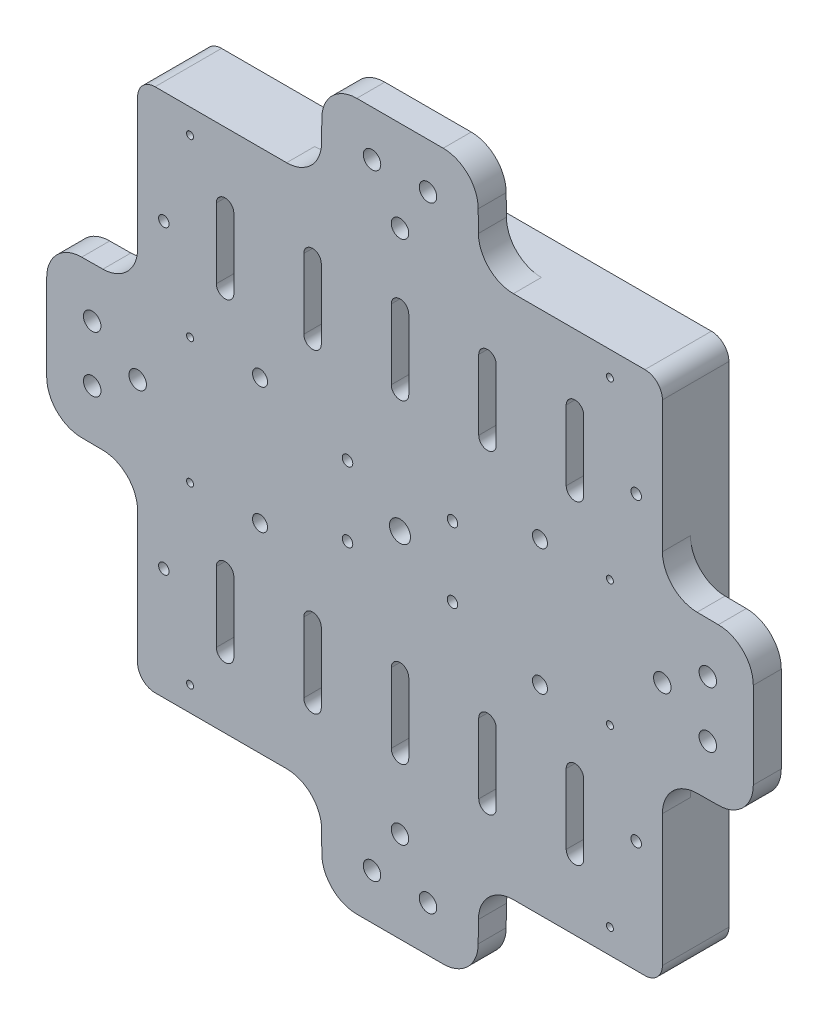
SolidWorks part; units mm, degrees
ref_plane "Front Plane" through (0, 0, 0) normal (0, 0, 1) x (1, 0, 0)
ref_plane "Top Plane" through (0, 0, 0) normal (0, 1, 0) x (1, 0, 0)
ref_plane "Right Plane" through (0, 0, 0) normal (1, 0, 0) x (0, 0, -1)
sketch "Sketch1" plane through (0, 0, 0) normal (0, 0, 1) x (1, 0, 0)
  line L13 (-90, -90) -> (90, -90)
  line L14 (-90, -90) -> (-90, 90)
  line L15 (-90, 90) -> (90, 90)
  line L16 (90, -90) -> (90, 90)
  line L17 (-90, -90) -> (90, 90) construction
  line L18 (-90, 90) -> (90, -90) construction
  line L19 (-75, -75) -> (75, -75)
  line L20 (-75, -75) -> (-75, 75)
  line L21 (-75, 75) -> (75, 75)
  line L22 (75, -75) -> (75, 75)
  line L23 (-75, -75) -> (75, 75) construction
  line L24 (-75, 75) -> (75, -75) construction
  line L39 (-75, -24.9122) -> (-75, 26.5574)
  line L40 (75, 22.5) -> (75, -22.5)
  line L41 (75, -22.5) -> (90.9698, -22.3479)
  line L42 (90.9698, -22.3479) -> (90.9698, 22.3479)
  line L43 (90.9698, 22.3479) -> (75, 22.5)
  line L44 (22.3479, -90.9698) -> (22.5, -75)
  line L45 (22.5, -75) -> (-22.5, -75)
  line L46 (-22.5, -75) -> (-22.3479, -90.9698)
  line L47 (-22.3479, -90.9698) -> (22.3479, -90.9698)
  line L48 (-90.9698, -22.3479) -> (-75, -22.5)
  line L49 (-75, -22.5) -> (-75, 22.5)
  line L50 (-75, 22.5) -> (-90.9698, 22.3479)
  line L51 (-90.9698, 22.3479) -> (-90.9698, -22.3479)
  line L52 (-22.3479, 90.9698) -> (-22.5, 75)
  line L53 (-22.5, 75) -> (22.5, 75)
  line L54 (22.5, 75) -> (22.3479, 90.9698)
  line L55 (22.3479, 90.9698) -> (-22.3479, 90.9698)
  line L64 (-72, -72) -> (-72, 72)
  line L65 (-72, 72) -> (72, 72)
  line L70 (72, -72) -> (72, 72)
  line L71 (-72, -72) -> (72, -72)
  line L72 (-10.5, -75) -> (10.5, -75)
  line L77 (75, -10.5) -> (64, -10.5)
  line L78 (75, -10.5) -> (75, 10.5)
  line L79 (75, 10.5) -> (64, 10.5)
  line L80 (64, -10.5) -> (64, 10.5)
  line L81 (-10.5, -75) -> (-10.5, -64)
  line L82 (-10.5, -64) -> (10.5, -64)
  line L83 (10.5, -75) -> (10.5, -64)
  line L84 (-75, 10.5) -> (-75, -10.5)
  line L85 (-75, 10.5) -> (-64, 10.5)
  line L86 (-64, 10.5) -> (-64, -10.5)
  line L87 (-75, -10.5) -> (-64, -10.5)
  line L88 (10.5, 75) -> (-10.5, 75)
  line L89 (10.5, 75) -> (10.5, 64)
  line L90 (10.5, 64) -> (-10.5, 64)
  line L91 (-10.5, 75) -> (-10.5, 64)
  line L92 (-75, 45) -> (-72, 45)
  line L93 (-45, 75) -> (-45, 72)
  circle A0 centre (87.9698, 8) radius 2.5
  circle A1 centre (74.9698, 0) radius 2.5
  circle A2 centre (87.9698, -8) radius 2.5
  circle A3 centre (8, -87.9698) radius 2.5
  circle A4 centre (0, -74.9698) radius 2.5
  circle A5 centre (-8, -87.9698) radius 2.5
  circle A6 centre (-87.9698, -8) radius 2.5
  circle A7 centre (-74.9698, 0) radius 2.5
  circle A8 centre (-87.9698, 8) radius 2.5
  circle A9 centre (-8, 87.9698) radius 2.5
  circle A10 centre (0, 74.9698) radius 2.5
  circle A11 centre (8, 87.9698) radius 2.5
  circle A12 centre (0, 0) radius 3
  point P0 (0, 0)
  point P11 (0, 0)
  point P74 (64, 0)
  point P85 (0, 0)
  dimension "D3" = 4
  dimension "D12" = 6
  dimension "D1" = 180
  dimension "D2" = 180
  dimension "D4" = 150
  dimension "D5" = 4
  dimension "D6" = 3
  dimension "D8" = 11
  dimension "D7" = 21
  dimension "D10" = 45
  dimension "D11" = 45
  dimension "D9" = 4
extrude "Boss-Extrude1" add sketch "Sketch1" along normal mid plane 8 contours L83 L19 L22 L77 L70 L71 | A2 L16 A0 L43 L22 L40 A1 L41 | L80 L77 L70 L79 | L91 L65 L64 L85 L86 L87 L71 L81 L82 L83 L70 L77 L80 L79 L89 L90 A12 | L21 L89 L65 L70 L79 L22 | L65 L91 L90 L89 | A10 L53 L91 L65 L89 | A11 L15 A9 L52 L21 L53 A10 L54 | A11 L15 L54 L55 L52 A9 | A8 L14 A6 L48 L39 L49 A7 L50 | L92 L20 L39 L85 L64 | L93 L21 L20 L92 L64 L65 | A5 L13 A3 L44 L19 L45 A4 L46 | A5 L13 L46 L47 L44 A3 | A4 L45 L83 L71 L81 | L71 L83 L82 L81 | A1 L40 L79 L70 L77 | A2 L16 L41 L42 L43 A0 | A8 L14 L50 L51 L48 A6 | L64 L87 L86 L85 | A7 L49 L87 L64 L85 | L87 L39 L20 L19 L81 L71 L64 | L21 L93 L65 L91 region at (0, -82.2708, 0) region at (0, -90.4981, 0) region at (-90.4981, 0, 0) region at (-82.2708, 0, 0) region at (-48.75, -74.0878, 0) region at (-10.2879, -73.5, 0) region at (-74.7879, -6.4999, 0) region at (0, -68, 0) region at (-41.25, -69.9635, 0) region at (-68, 0, 0) region at (41.25, -72.9122, 0) region at (-73.5, 27.75, 0) region at (82.2708, 0, 0) region at (90.4981, 0, 0) region at (0, 90.4981, 0) region at (0, 82.2708, 0) region at (-73.5, 45.4243, 0) region at (68, 0, 0) region at (72.2121, 0, 0) region at (-27.75, 73.5, 0) region at (72.9122, 41.25, 0) region at (-6.4999, 74.7879, 0) region at (0, 68, 0)
extrude "Boss-Extrude3" add sketch "Sketch1<4>" against normal blind 15 contours L93 L21 L20 L92 L64 L65 | L87 L39 L20 L19 L81 L71 L64 | L21 L89 L65 L70 L79 L22 | L83 L19 L22 L77 L70 L71 | L21 L93 L65 L91 | L92 L20 L39 L85 L64 region at (-48.75, -74.0878, 0) region at (41.25, -72.9122, 0) region at (-73.5, 27.75, 0) region at (-73.5, 45.4243, 0) region at (-27.75, 73.5, 0) region at (72.9122, 41.25, 0)
sketch "Sketch1<4>" plane through (0, 0, 0) normal (0, 0, 1) x (1, 0, 0) same geometry as "Sketch1"
sketch "Sketch6" plane through (0, 0, 0) normal (0, 0, 1) x (1, 0, 0)
  line L0 (-25, 55) -> (-25, 35) construction
  line L12 (-40, 18) -> (40, 18) construction
  line L14 (10.45, 0) -> (-10.45, 0) construction
  line L15 (-40, -18) -> (40, -18) construction
  line L17 (-15, -10) -> (15, -10) construction
  line L18 (-15, -10) -> (-15, 10) construction
  line L19 (-15, 10) -> (15, 10) construction
  line L20 (15, -10) -> (15, 10) construction
  line L21 (-15, -10) -> (15, 10) construction
  line L22 (-15, 10) -> (15, -10) construction
  line L23 (-50, 55) -> (-50, 35) construction
  line L24 (-47.5, 55) -> (-47.5, 35)
  line L25 (-52.5, 55) -> (-52.5, 35)
  line L26 (-22.5, 55) -> (-22.5, 35)
  line L29 (-27.5, 55) -> (-27.5, 35)
  line L30 (0, 55) -> (0, 35) construction
  line L31 (2.5, 55) -> (2.5, 35)
  line L32 (-2.5, 55) -> (-2.5, 35)
  line L33 (25, 55) -> (25, 35) construction
  line L34 (27.5, 55) -> (27.5, 35)
  line L35 (22.5, 55) -> (22.5, 35)
  line L36 (50, 55) -> (50, 35) construction
  line L37 (52.5, 55) -> (52.5, 35)
  line L38 (47.5, 55) -> (47.5, 35)
  line L39 (41.0975, 0) -> (-41.0975, 0) construction
  line L40 (-50, -55) -> (-50, -35) construction
  line L41 (-47.5, -55) -> (-47.5, -35)
  line L42 (-52.5, -55) -> (-52.5, -35)
  line L43 (-25, -55) -> (-25, -35) construction
  line L44 (-22.5, -55) -> (-22.5, -35)
  line L45 (-27.5, -55) -> (-27.5, -35)
  line L46 (0, -55) -> (0, -35) construction
  line L47 (2.5, -55) -> (2.5, -35)
  line L48 (-2.5, -55) -> (-2.5, -35)
  line L49 (25, -55) -> (25, -35) construction
  line L50 (27.5, -55) -> (27.5, -35)
  line L51 (22.5, -55) -> (22.5, -35)
  line L52 (50, -55) -> (50, -35) construction
  line L53 (52.5, -55) -> (52.5, -35)
  line L54 (47.5, -55) -> (47.5, -35)
  circle A8 centre (40, 18) radius 2.15
  circle A9 centre (-40, 18) radius 2.15
  circle A10 centre (40, -18) radius 2.15
  circle A11 centre (-40, -18) radius 2.15
  circle A12 centre (-15, 10) radius 1.5
  circle A13 centre (-15, -10) radius 1.5
  circle A14 centre (15, -10) radius 1.5
  circle A15 centre (15, 10) radius 1.5
  arc A16 (-47.5, 55) -> (-52.5, 55) centre (-50, 55) ccw
  arc A17 (-52.5, 35) -> (-47.5, 35) centre (-50, 35) ccw
  arc A20 (-22.5, 55) -> (-27.5, 55) centre (-25, 55) ccw
  arc A21 (-27.5, 35) -> (-22.5, 35) centre (-25, 35) ccw
  arc A22 (2.5, 55) -> (-2.5, 55) centre (0, 55) ccw
  arc A23 (-2.5, 35) -> (2.5, 35) centre (0, 35) ccw
  arc A24 (27.5, 55) -> (22.5, 55) centre (25, 55) ccw
  arc A25 (22.5, 35) -> (27.5, 35) centre (25, 35) ccw
  arc A26 (52.5, 55) -> (47.5, 55) centre (50, 55) ccw
  arc A27 (47.5, 35) -> (52.5, 35) centre (50, 35) ccw
  arc A28 (-47.5, -55) -> (-52.5, -55) centre (-50, -55) cw
  arc A29 (-52.5, -35) -> (-47.5, -35) centre (-50, -35) cw
  arc A30 (-22.5, -55) -> (-27.5, -55) centre (-25, -55) cw
  arc A31 (-27.5, -35) -> (-22.5, -35) centre (-25, -35) cw
  arc A32 (2.5, -55) -> (-2.5, -55) centre (0, -55) cw
  arc A33 (-2.5, -35) -> (2.5, -35) centre (0, -35) cw
  arc A34 (27.5, -55) -> (22.5, -55) centre (25, -55) cw
  arc A35 (22.5, -35) -> (27.5, -35) centre (25, -35) cw
  arc A36 (52.5, -55) -> (47.5, -55) centre (50, -55) cw
  arc A37 (47.5, -35) -> (52.5, -35) centre (50, -35) cw
  point P3 (-25, 45)
  point P10 (0, 45)
  point P17 (25, 45)
  point P24 (50, 45)
  point P32 (0, 18)
  point P41 (0, 0)
  point P51 (-50, 45)
  point P60 (-50, -45)
  point P67 (-25, -45)
  point P74 (0, -45)
  point P81 (25, -45)
  point P88 (50, -45)
  dimension "D13" = 4.3
  dimension "D14" = 4.3
  dimension "D17" = 3
  dimension "D9" = 20
  dimension "D3" = 5
  dimension "D5" = 5
  dimension "D7" = 50
  dimension "D15" = 80
  dimension "D16" = 18
  dimension "D21" = 30
  dimension "D22" = 20
extrude "Cut-Extrude3" cut sketch "Sketch6" against normal mid plane 10
sketch "Sketch7" plane through (0, 0, 0) normal (0, 0, 1) x (1, 0, 0)
  line L0 (-90.9698, 22.3479) -> (-90.9698, -22.3479) construction
  line L1 (-100.9698, -22.3479) -> (-90.9698, -22.3479)
  line L2 (-100.9698, -22.3479) -> (-100.9698, 22.3479)
  line L3 (-100.9698, 22.3479) -> (-90.9698, 22.3479)
  line L4 (-90.9698, -22.3479) -> (-90.9698, 22.3479)
  line L5 (-100.9698, -22.3479) -> (-90.9698, 22.3479) construction
  line L6 (-100.9698, 22.3479) -> (-90.9698, -22.3479) construction
  line L7 (100.9698, -22.3479) -> (90.9698, -22.3479)
  line L8 (100.9698, -22.3479) -> (100.9698, 22.3479)
  line L9 (100.9698, 22.3479) -> (90.9698, 22.3479)
  line L10 (90.9698, -22.3479) -> (90.9698, 22.3479)
  line L11 (100.9698, -22.3479) -> (90.9698, 22.3479) construction
  line L12 (100.9698, 22.3479) -> (90.9698, -22.3479) construction
  line L17 (22.3479, 90.9698) -> (-22.3479, 90.9698) construction
  line L18 (-22.3479, 100.9698) -> (22.3479, 100.9698)
  line L19 (-22.3479, 100.9698) -> (-22.3479, 90.9698)
  line L20 (-22.3479, 90.9698) -> (22.3479, 90.9698)
  line L21 (22.3479, 100.9698) -> (22.3479, 90.9698)
  line L22 (-22.3479, 100.9698) -> (22.3479, 90.9698) construction
  line L23 (-22.3479, 90.9698) -> (22.3479, 100.9698) construction
  line L24 (22.3479, -100.9698) -> (-22.3479, -100.9698)
  line L25 (22.3479, -100.9698) -> (22.3479, -90.9698)
  line L26 (22.3479, -90.9698) -> (-22.3479, -90.9698)
  line L27 (-22.3479, -100.9698) -> (-22.3479, -90.9698)
  line L28 (22.3479, -100.9698) -> (-22.3479, -90.9698) construction
  line L29 (22.3479, -90.9698) -> (-22.3479, -100.9698) construction
  line L30 (90.9698, -22.3479) -> (90.9698, 22.3479) construction
  line L31 (-22.3479, -90.9698) -> (22.3479, -90.9698) construction
  point P0 (-95.9698, 0)
  point P6 (95.9698, 0)
  point P13 (0, -95.9698)
  point P17 (0, 95.9698)
  dimension "D1" = 10
  dimension "D2" = 44.6958
  dimension "D3" = 10
  dimension "D4" = 10
  dimension "D5" = 10
  dimension "D6" = 44.6958
  dimension "D7" = 44.6958
  dimension "D8" = 44.6958
extrude "Boss-Extrude4" add sketch "Sketch7" along normal up to surface (4 mm away) from surface contours L1 L4 L3 L2 | L21 L18 L19 L20 | L10 L7 L8 L9 | L27 L24 L25 L26 region at (-95.9698, 0, 0) region at (95.9698, 0, 0) region at (0, 95.9698, 0) region at (0, -95.9698, 0) up to face at (25, -45, 4) starting at face at (25, -45, -4)
sketch "Sketch8" [suppressed] plane through (0, 0, 0) normal (0, 0, 1) x (1, 0, 0)
  line L0 (10.5, 75) -> (75, 75) construction
  line L1 (10.5, 72) -> (72, 72) construction
  line L2 (10.5, 75) -> (10.5, 72) construction
  line L3 (75, 10.5) -> (75, 75) construction
  line L4 (72, 10.5) -> (72, 72) construction
  line L5 (10.5, -75) -> (10.5, -72) construction
  line L6 (10.5, -72) -> (72, -72) construction
  line L7 (72, -72) -> (72, -10.5) construction
  line L8 (72, -10.5) -> (75, -10.5) construction
  line L9 (75, -10.5) -> (75, -75) construction
  line L10 (75, -75) -> (10.5, -75) construction
  line L11 (-75, -10.5) -> (-72, -10.5) construction
  line L12 (-72, -10.5) -> (-72, -72) construction
  line L13 (-72, -72) -> (-10.5, -72) construction
  line L14 (-10.5, -72) -> (-10.5, -75) construction
  line L15 (-10.5, -75) -> (-75, -75) construction
  line L16 (-75, -75) -> (-75, -10.5) construction
  line L17 (-72, 10.5) -> (-72, 72) construction
  line L18 (-75, 10.5) -> (-75, 75) construction
  line L19 (-10.5, 75) -> (-10.5, 72) construction
  line L20 (-72, 72) -> (-10.5, 72) construction
  line L21 (-75, 75) -> (-10.5, 75) construction
  line L22 (10.5, -75) -> (10.5, -72)
  line L23 (10.5, -72) -> (72, -72)
  line L24 (72, -72) -> (72, -10.5)
  line L25 (72, -10.5) -> (75, -10.5)
  line L26 (75, -10.5) -> (75, -75)
  line L27 (75, -75) -> (10.5, -75)
  line L28 (-75, -10.5) -> (-72, -10.5)
  line L29 (-72, -10.5) -> (-72, -72)
  line L30 (-72, -72) -> (-10.5, -72)
  line L31 (-10.5, -72) -> (-10.5, -75)
  line L32 (-10.5, -75) -> (-75, -75)
  line L33 (-75, -75) -> (-75, -10.5)
  line L34 (-72, 10.5) -> (-72, 72)
  line L35 (-75, 10.5) -> (-75, 75)
  line L36 (-10.5, 75) -> (-10.5, 72)
  line L37 (-72, 72) -> (-10.5, 72)
  line L38 (-75, 75) -> (-10.5, 75)
  line L39 (10.5, 75) -> (75, 75)
  line L40 (72, 10.5) -> (72, 72)
  line L41 (75, 10.5) -> (75, 75)
  line L42 (10.5, 75) -> (10.5, 72)
  line L43 (10.5, 72) -> (72, 72)
  line L44 (-75, 10.5) -> (-72, 10.5)
  line L45 (75, 10.5) -> (72, 10.5)
fillet "Fillet1" radius 10 16 edges at (22.5, -75, 0) (-22.5, -75, 0) (-22.5, 75, 0) (22.5, 75, 0) (75, 22.5, 0) (75, -22.5, 0) (-75, -22.5, 0) (-75, 22.5, 0) (22.3479, 100.9698, 0) (-22.3479, 100.9698, 0) (-100.9698, 22.3479, 0) (-100.9698, -22.3479, 0) (-22.3479, -100.9698, 0) (22.3479, -100.9698, 0) (100.9698, -22.3479, 0) (100.9698, 22.3479, 0)
fillet "Fillet2" [suppressed] radius 5
fillet "Fillet3" radius 5 4 edges at (75, 75, -5.5) (-75, 75, -5.5) (-75, -75, -5.5) (75, -75, -5.5)
sketch "Sketch9" plane through (0, 0, 0) normal (0, 0, 1) x (1, 0, 0)
  line L0 (67.5, 43) -> (-67.5, 43) construction
  line L1 (-60, 68) -> (60, 68) construction
  line L2 (-60, 68) -> (-60, 18) construction
  line L3 (-60, 18) -> (60, 18) construction
  line L4 (60, 68) -> (60, 18) construction
  line L5 (41.0975, 0) -> (-41.0975, 0) construction
  line L6 (-60, -68) -> (-60, -18) construction
  line L7 (-60, -18) -> (60, -18) construction
  line L8 (60, -68) -> (60, -18) construction
  line L9 (-60, -68) -> (60, -68) construction
  circle A0 centre (-60, 68) radius 1
  circle A1 centre (-60, 18) radius 1
  circle A2 centre (60, 18) radius 1
  circle A3 centre (60, 68) radius 1
  circle A4 centre (67.5, 43) radius 1.5
  circle A5 centre (-67.5, 43) radius 1.5
  circle A6 centre (-60, -18) radius 1
  circle A7 centre (60, -18) radius 1
  circle A8 centre (-60, -68) radius 1
  circle A9 centre (-67.5, -43) radius 1.5
  circle A10 centre (60, -68) radius 1
  circle A11 centre (67.5, -43) radius 1.5
  point P8 (0, 68)
  point P11 (0, 0)
  point P14 (-55.8045, 43)
  point P16 (-60, 43)
  point P17 (0, 43)
  dimension "D1" = 2
  dimension "D6" = 3
  dimension "D7" = 3
  dimension "D2" = 120
  dimension "D3" = 68
  dimension "D4" = 50
  dimension "D5" = 135
extrude "Cut-Extrude4" cut sketch "Sketch9" against normal mid plane 10
